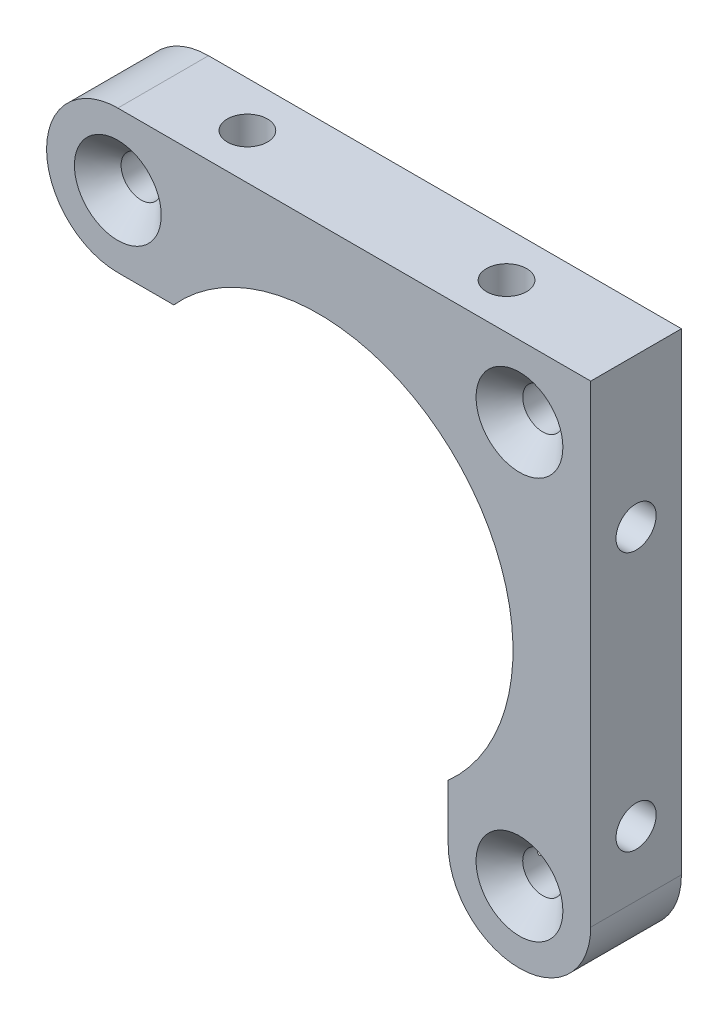
SolidWorks part; units mm, degrees
ref_plane "Front Plane" through (0, 0, 0) normal (0, 0, 1) x (1, 0, 0)
ref_plane "Top Plane" through (0, 0, 0) normal (0, 1, 0) x (1, 0, 0)
ref_plane "Right Plane" through (0, 0, 0) normal (1, 0, 0) x (0, 0, -1)
sketch "Sketch1" plane through (0, 0, 0) normal (0, 0, 1) x (1, 0, 0)
  line L0 (-21, 21) -> (21, 21) construction
  line L1 (-21, 21) -> (-21, -21) construction
  line L2 (21, 21) -> (21, -21) construction
  line L3 (-21, -21) -> (21, -21) construction
  line L4 (-21, 21) -> (21, -21) construction
  line L5 (21, 21) -> (-21, -21) construction
  line L6 (10, -15.5) -> (10, -11.1803)
  line L7 (-15.5, 10) -> (-11.1803, 10)
  line L8 (-15.5, 21) -> (21, 21)
  line L9 (21, 21) -> (21, -15.5)
  line L12 (15.5, 15.5) -> (15.5, -15.5) construction
  line L13 (15.5, 15.5) -> (-22.9774, 15.5) construction
  circle A0 centre (0, 0) radius 11 construction
  arc A1 (10, -11.1803) -> (-11.1803, 10) centre (0, 0) ccw
  circle A2 centre (15.5, 15.5) radius 1.55
  circle A3 centre (15.5, -15.5) radius 1.55
  circle A4 centre (-15.5, 15.5) radius 1.55
  arc A5 (10, -15.5) -> (21, -15.5) centre (15.5, -15.5) ccw
  arc A6 (-15.5, 21) -> (-15.5, 10) centre (-15.5, 15.5) ccw
  point P1 (0, 0)
  dimension "D2" = 22
  dimension "D3" = 3.1
  dimension "D7" = 15
  dimension "D1" = 42
  dimension "D4" = 31
extrude "Boss-Extrude1" add sketch "Sketch1" along normal blind 7
sketch "Sketch2" plane through (0, 21, 0) normal (0, 1, 0) x (1, 0, 0)
  line L0 (21, -3.5) -> (-9, -3.5) construction
  line L1 (21, -7) -> (21, 0) construction
  circle A0 centre (-9, -3.5) radius 1.55
  circle A1 centre (11, -3.5) radius 1.55
  dimension "D1" = 3.1
  dimension "D3" = 10
  dimension "D2" = 20
extrude "Cut-Extrude1" cut sketch "Sketch2" against normal through all
sketch "Sketch4" plane through (21, 0, 0) normal (1, 0, 0) x (0, 0, -1)
  line L0 (9, -10.5) -> (-3.5, -10.5) construction
  line L3 (-3.5, 21) -> (-3.5, 9.5) construction
  line L4 (-7, 21) -> (0, 21) construction
  circle A0 centre (-3.5, -10.5) radius 1.55
  circle A1 centre (-3.5, 9.5) radius 1.55
  dimension "D1" = 3.1
  dimension "D4" = 10.5
  dimension "D3" = 20
extrude "Cut-Extrude2" cut sketch "Sketch4" against normal through all
sketch "Sketch5" plane through (0, 21, 0) normal (0, 1, 0) x (1, 0, 0)
  line L0 (-12, -3.5) -> (-12, 2.1732)
  line L1 (-12, 2.1732) -> (-6, 2.1732)
  line L2 (-6, 2.1732) -> (-6, -3.5)
  line L3 (8, -3.5) -> (8, 2.1892)
  line L4 (8, 2.1892) -> (14, 2.1892)
  line L5 (14, 2.1892) -> (14, -3.5)
  arc A0 (8, -3.5) -> (14, -3.5) centre (11, -3.5) ccw
  arc A1 (-12, -3.5) -> (-6, -3.5) centre (-9, -3.5) ccw
  circle A2 centre (-9, -3.5) radius 1.55 construction
  circle A3 centre (11, -3.5) radius 1.55 construction
  arc A4 (-6, -3.5) -> (-12, -3.5) centre (-9, -3.5) ccw construction
  arc A5 (14, -3.5) -> (8, -3.5) centre (11, -3.5) ccw construction
  dimension "D1" = 6
extrude "Cut-Extrude3" cut sketch "Sketch5" against normal through all from offset 7 offset against normal yes
chamfer "Chamfer1" distance 1.8 angle 45 3 edges at (17.05, -15.5, 7) (-13.95, 15.5, 7) (17.05, 15.5, 7)
chamfer "Chamfer2" distance 1.8 angle 45 2 edges at (9.45, 14, 3.5) (-10.55, 14, 3.5)
sketch "Sketch6" plane through (21, 0, 0) normal (-1, 0, 0) x (0, 0, 1)
  line L0 (3.5, -7.15) -> (0, -7.15)
  line L2 (0, -15.1095) -> (0, -5.3852) construction
  line L4 (0, -7.15) -> (0, -13.85)
  line L5 (0, -13.85) -> (3.5, -13.85)
  line L6 (3.5, 12.85) -> (0, 12.85)
  line L7 (0, 21) -> (0, 10) construction
  line L8 (0, 12.85) -> (0, 6.15)
  line L9 (0, 5.3852) -> (0, 14) construction
  line L10 (0, 6.15) -> (3.5, 6.15)
  arc A2 (3.5, -13.85) -> (3.5, -7.15) centre (3.5, -10.5) ccw
  arc A3 (3.5, 6.15) -> (3.5, 12.85) centre (3.5, 9.5) ccw
  dimension "D1" = 6.7
extrude "Cut-Extrude4" cut sketch "Sketch6" along normal through all from offset 5
chamfer "Chamfer3" distance 1.8 angle 45 2 edges at (16, -10.5, 5.05) (16, 9.5, 5.05)
